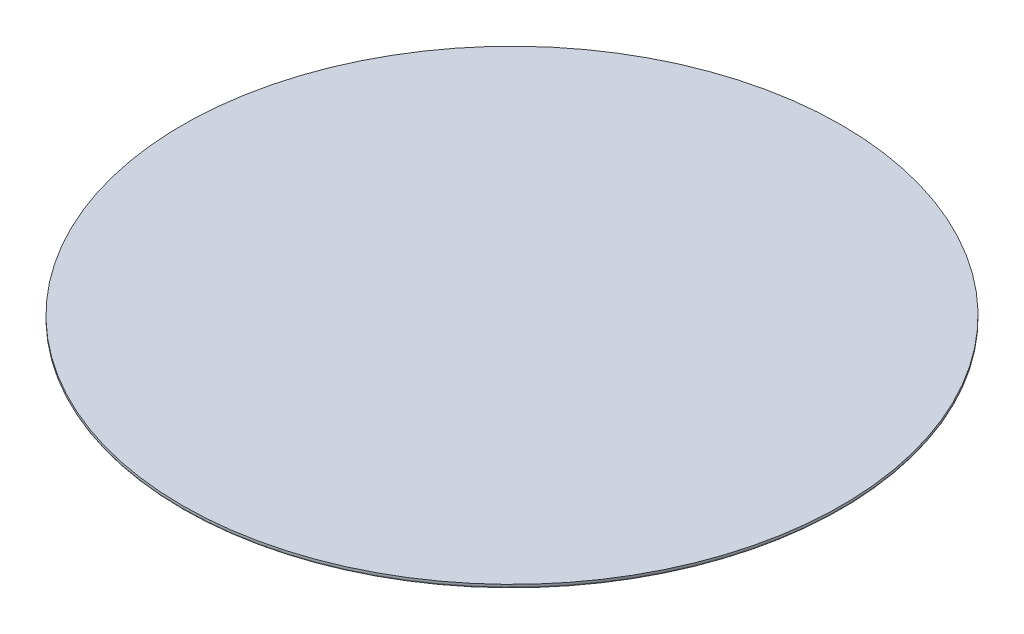
SolidWorks part; units mm, degrees
material "Калифорния"
ref_plane "Спереди" through (0, 0, 0) normal (0, 0, 1) x (1, 0, 0)
ref_plane "Сверху" through (0, 0, 0) normal (0, 1, 0) x (1, 0, 0)
ref_plane "Справа" through (0, 0, 0) normal (1, 0, 0) x (0, 0, -1)
sketch "Эскиз1" plane through (0, 0, 0) normal (0, 1, 0) x (1, 0, 0)
  circle A0 centre (0, 0) radius 45
  dimension "D1" = 90
extrude "Бобышка-Вытянуть1" add sketch "Эскиз1" along normal blind 0.5
fillet "Скругление3" radius 0.2 1 edges at (0, 0, 45)
dome "Купол2" faces to dome 1 distance 10 reverse direction no elliptical dome no face at (0, 0, 44.8) parameters "D1"=10
